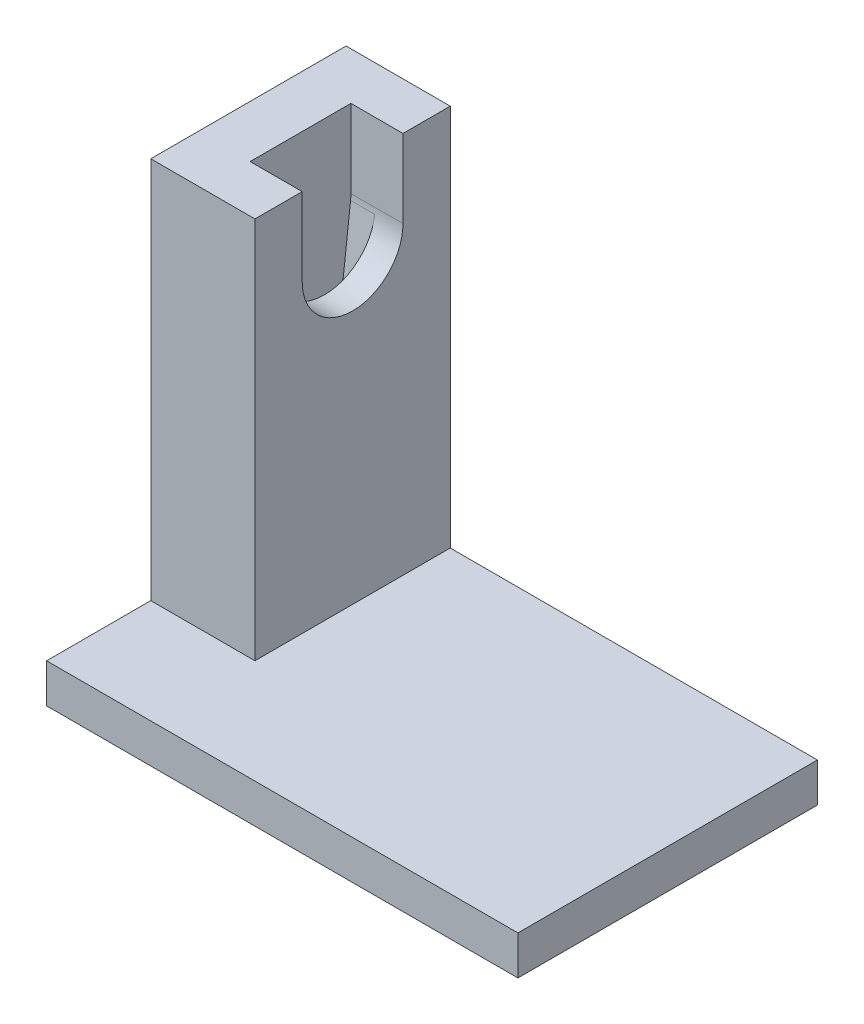
SolidWorks part; units mm, degrees
ref_plane "Front Plane" through (0, 0, 0) normal (0, 0, 1) x (1, 0, 0)
ref_plane "Top Plane" through (0, 0, 0) normal (0, 1, 0) x (1, 0, 0)
ref_plane "Right Plane" through (0, 0, 0) normal (1, 0, 0) x (0, 0, -1)
ref_axis "Axis1" through (-88.99, 0, 0) along (1, 0, 0)
sketch "Sketch1" plane through (0, 0, 0) normal (1, 0, 0) x (0, 0, -1)
  line L2 (0, 0) -> (0, 6) construction
  line L3 (7.5, 6) -> (-7.5, 6)
  line L6 (7.5, 6) -> (7.5, -26.3871)
  line L7 (7.5, -26.3871) -> (-7.5, -26.3871)
  line L8 (-7.5, 6) -> (-7.5, -26.3871)
  line L9 (0, 0) -> (7.5, 0) construction
  line L10 (0, -22.3871) -> (0, -26.3871) construction
  circle A2 centre (0, 0) radius 22.3871 construction
  dimension "D1" = 15
  dimension "D2" = 4
  dimension "D3" = 6
extrude "Boss-Extrude1" add sketch "Sketch1" against normal mid plane 8
sketch "Sketch2" plane through (4, 0, 0) normal (1, 0, 0) x (0, 0, -1)
  line L0 (7.5, -26.3871) -> (7.5, 6) construction
  line L1 (7.5, -23.3871) -> (-7.5, -23.3871)
  line L2 (7.5, -23.3871) -> (7.5, -26.3871)
  line L3 (7.5, -26.3871) -> (-7.5, -26.3871)
  line L4 (-7.5, -23.3871) -> (-7.5, -26.3871)
  dimension "D1" = 3
extrude "Boss-Extrude2" add sketch "Sketch2" along normal up to surface (28.1955 mm away)
sketch "Sketch3" plane through (0, 0, 0) normal (1, 0, 0) x (0, 0, -1)
  line L0 (2.2351, -14.3389) -> (3.8443, -0.4453)
  line L1 (-3.8443, -0.4453) -> (-2.2351, -14.3389)
  line L2 (1.9867, -14.3101) -> (3.596, -0.4165)
  line L3 (-3.596, -0.4165) -> (-1.9867, -14.3101)
  line L4 (1.9867, -14.3101) -> (3.596, -0.4165) construction
  line L5 (-3.596, -0.4165) -> (-1.9867, -14.3101) construction
  line L6 (-3.87, 0) -> (-3.87, 6)
  line L7 (-3.87, 6) -> (3.87, 6)
  line L8 (3.87, 6) -> (3.87, 0)
  line L9 (7.5, 6) -> (-7.5, 6) construction
  arc A0 (3.8443, -0.4453) -> (3.87, 0) centre (0, 0) ccw
  arc A1 (-2.2351, -14.3389) -> (2.2351, -14.3389) centre (0, -14.08) ccw
  arc A2 (-1.9867, -14.3101) -> (1.9867, -14.3101) centre (0, -14.08) ccw
  arc A3 (3.596, -0.4165) -> (-3.596, -0.4165) centre (0, 0) ccw
  arc A4 (-1.9867, -14.3101) -> (1.9867, -14.3101) centre (0, -14.08) ccw construction
  arc A5 (3.596, -0.4165) -> (-3.596, -0.4165) centre (0, 0) ccw construction
  arc A6 (-3.87, 0) -> (-3.8443, -0.4453) centre (0, 0) ccw
  arc A7 (3.8443, -0.4453) -> (-3.8443, -0.4453) centre (0, 0) ccw construction
  dimension "D1" = 0
  dimension "D2" = 0.25
extrude "Cut-Extrude1" cut sketch "Sketch3" along normal offset from surface (1.85 mm away) 0.25 offset beyond the face yes
sketch "Sketch4" plane through (0, 0, 0) normal (1, 0, 0) x (0, 0, -1)
  line L0 (3.87, 0) -> (3.87, 6) construction
  line L1 (-3.87, 6) -> (-3.87, 0) construction
  line L2 (3.87, 0) -> (3.87, 6)
  line L3 (-3.87, 6) -> (-3.87, 0)
  line L4 (3.87, 6) -> (-3.87, 6) construction
  line L5 (3.87, 6) -> (-3.87, 6)
  circle A2 centre (0, 0) radius 3.87
  arc A3 (-3.87, 0) -> (3.87, 0) centre (0, 0) ccw
  dimension "D1" = 0.25
extrude "Cut-Extrude2" cut sketch "Sketch4" along normal up to surface (4 mm away) up to face at (4, -8.6936, 0)
sketch "Sketch5" plane through (4, 0, 0) normal (1, 0, 0) x (0, 0, -1)
  line L1 (-7.5, -23.3871) -> (-4.5, -23.3871)
  line L2 (-7.5, -23.3871) -> (-7.5, -19.3871)
  line L3 (-7.5, -19.3871) -> (-4.5, -19.3871)
  line L4 (-4.5, -23.3871) -> (-4.5, -19.3871)
  line L5 (7.5, -23.3871) -> (4.5, -23.3871)
  line L6 (7.5, -23.3871) -> (7.5, -19.3871)
  line L7 (7.5, -19.3871) -> (4.5, -19.3871)
  line L8 (4.5, -23.3871) -> (4.5, -19.3871)
  dimension "D1" = 4
  dimension "D2" = 3
extrude "Boss-Extrude3" [suppressed] add sketch "Sketch5" along normal up to surface (28.1955 mm away) up to face at (32.1955, -24.8871, 0)
sketch "Sketch6" plane through (0, -26.3871, 0) normal (0, -1, 0) x (1, 0, 0)
  line L0 (-4, 7.5) -> (32.1955, 7.5) construction
  line L2 (0, 0) -> (-16.6927, 0) construction
  line L7 (-4, 7.5) -> (32.1955, 7.5)
  line L8 (32.1955, 7.5) -> (32.1955, 15.5)
  line L10 (32.1955, 15.5) -> (-4, 15.5)
  line L11 (-4, 15.5) -> (-4, 7.5)
  dimension "D1" = 8
extrude "Boss-Extrude4" add sketch "Sketch6" against normal up to surface (3 mm away) up to face at (18.0978, -23.3871, 0)
